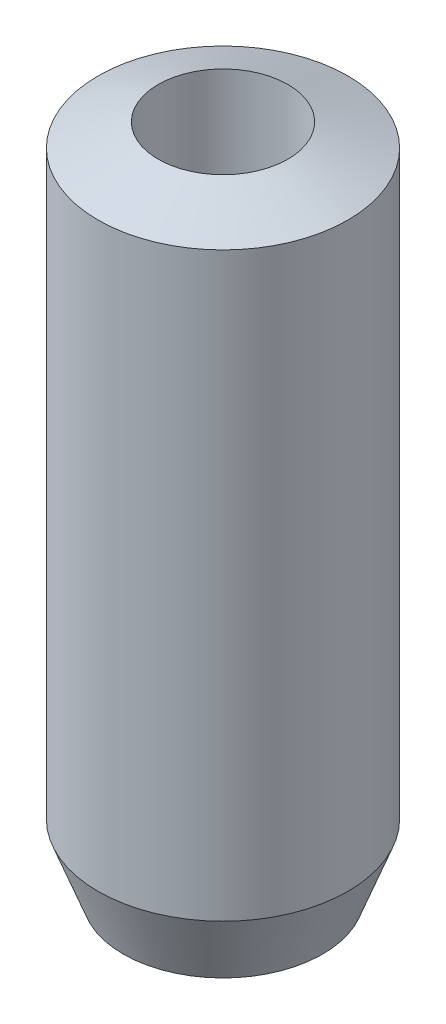
SolidWorks part; units mm, degrees
ref_plane "Front Plane" through (0, 0, 0) normal (0, 0, 1) x (1, 0, 0)
ref_plane "Top Plane" through (0, 0, 0) normal (0, 1, 0) x (1, 0, 0)
ref_plane "Right Plane" through (0, 0, 0) normal (1, 0, 0) x (0, 0, -1)
sketch "Sketch1" plane through (0, 0, 0) normal (0, 1, 0) x (1, 0, 0)
  circle A0 centre (0, 0) radius 15
  dimension "SHAFT_OD" = 30
extrude "Boss-Extrude1" add sketch "Sketch1" along normal blind 80.9016
sketch "Sketch2" plane through (0, 0, 0) normal (0, 1, 0) x (1, 0, 0)
  circle A0 centre (0, 0) radius 7.7838
  dimension "BORE_D" = 15.5676
extrude "Cut-Extrude1" cut sketch "Sketch2" along normal through all
chamfer "Chamfer1" distance 3.03 angle 69.361 2 edges at (0, 80.9016, 15) (0, 0, 15) first distance on face at (0, 80.9016, 15) first distance on face at (0, 0, 7.7838)
